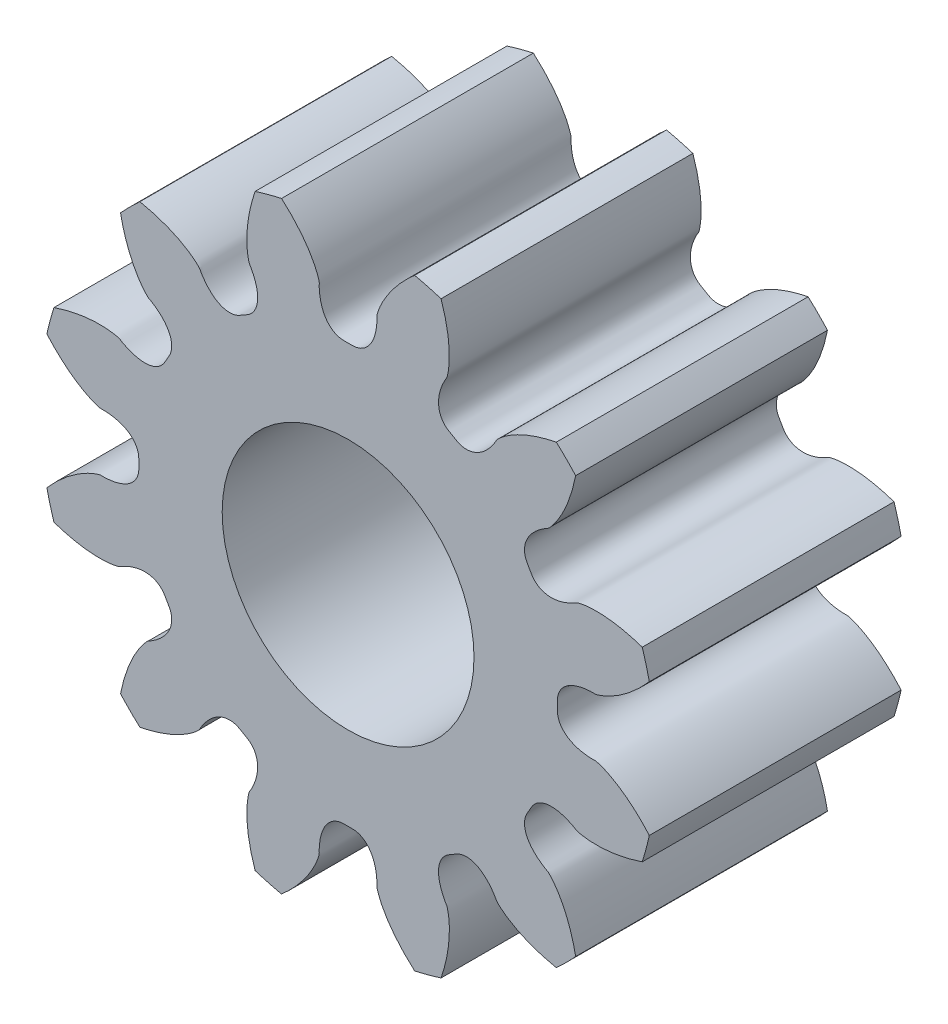
SolidWorks part; units mm, degrees
ref_plane "Front" through (0, 0, 0) normal (0, 0, 1) x (1, 0, 0)
ref_plane "Top" through (0, 0, 0) normal (0, 1, 0) x (1, 0, 0)
ref_plane "Right" through (0, 0, 0) normal (1, 0, 0) x (0, 0, -1)
ref_axis "Axis1" through (0, 0, 50) along (0, 0, -1)
sketch "SketchRevolveSpur01" plane through (0, 0, 0) normal (1, 0, 0) x (0, 0, -1)
  line L0 (0, 0) -> (1, 0) construction
  line L1 (-3, 0) -> (-3, 7.35)
  line L2 (-3, 7.35) -> (3, 7.35)
  line L3 (3, 7.35) -> (3, 0)
  line L4 (3, 0) -> (-3, 0)
  dimension "Side1" = 3
  dimension "OutsideRadius" = 7.35
  dimension "Side2" = 3
revolve "Spur01" add sketch "SketchRevolveSpur01" angle 360 about L0
sketch "SketchToothSpur01" plane through (0, 0, 0) normal (0, 0, 1) x (1, 0, 0)
  arc A0 (7.2196, 1.6352) -> (7.2196, -1.6352) centre (0, 0) cw
  spline S0 degree 3 poles (7.2196, -1.6352) (7.1512, -1.5547) (7.0472, -1.4407) (6.9039, -1.3008) (6.8019, -1.2084) (6.7029, -1.1253) (6.6074, -1.051) (6.5159, -0.9853) (6.4291, -0.9276) (6.3472, -0.8776) (6.2708, -0.8348) (6.2003, -0.7986) (6.136, -0.7687) (6.0784, -0.7445) (6.0276, -0.7251) (5.9684, -0.706) (5.9004, -0.6821) (5.8258, -0.69) (5.7634, -0.6863) (5.7097, -0.6827) (5.6575, -0.6771) (5.6068, -0.6697) (5.5575, -0.6606) (5.5097, -0.6498) (5.4633, -0.6371) (5.4183, -0.6226) (5.3747, -0.6063) (5.3325, -0.5879) (5.2917, -0.5674) (5.2522, -0.5447) (5.2142, -0.5194) (5.1776, -0.4914) (5.1428, -0.4603) (5.1098, -0.4258) (5.0793, -0.3877) (5.0516, -0.3455) (5.0276, -0.2994) (5.0082, -0.2493) (4.9943, -0.1958) (4.988, -0.1455) (4.9854, -0.08) (4.989, 0) (4.9854, 0.08) (4.988, 0.1455) (4.9943, 0.1958) (5.0082, 0.2493) (5.0276, 0.2994) (5.0516, 0.3455) (5.0793, 0.3877) (5.1098, 0.4258) (5.1428, 0.4603) (5.1776, 0.4914) (5.2142, 0.5194) (5.2522, 0.5447) (5.2917, 0.5674) (5.3325, 0.5879) (5.3747, 0.6063) (5.4183, 0.6226) (5.4633, 0.6371) (5.5097, 0.6498) (5.5575, 0.6606) (5.6068, 0.6697) (5.6575, 0.6771) (5.7097, 0.6827) (5.7634, 0.6863) (5.8258, 0.69) (5.9004, 0.6821) (5.9684, 0.706) (6.0276, 0.7251) (6.0784, 0.7445) (6.136, 0.7687) (6.2003, 0.7986) (6.2708, 0.8348) (6.3472, 0.8776) (6.4291, 0.9276) (6.5159, 0.9853) (6.6074, 1.051) (6.7029, 1.1253) (6.8019, 1.2084) (6.9039, 1.3008) (7.0472, 1.4407) (7.1512, 1.5547) (7.2196, 1.6352) knots 0 0 0 0 0.053494 0.07813 0.101357 0.123177 0.143589 0.162594 0.180191 0.19638 0.211161 0.224534 0.2365 0.247058 0.256209 0.263951 0.278695 0.292012 0.301319 0.310395 0.31925 0.327895 0.336345 0.344615 0.352721 0.360686 0.368533 0.376288 0.383984 0.391656 0.399345 0.407095 0.414956 0.422977 0.431208 0.439691 0.448455 0.457508 0.466829 0.476365 0.48311 0.5 0.51689 0.523635 0.533171 0.542492 0.551545 0.560309 0.568792 0.577023 0.585044 0.592905 0.600655 0.608344 0.616016 0.623712 0.631467 0.639314 0.647279 0.655385 0.663655 0.672105 0.68075 0.689605 0.698681 0.707988 0.721305 0.736049 0.743791 0.752942 0.7635 0.775466 0.788839 0.80362 0.819809 0.837406 0.856411 0.876823 0.898643 0.92187 0.946506 1 1 1 1
extrude "ToothExtrudeCutSpur01" cut sketch "SketchToothSpur01" against normal blind 3 and the other way blind 3
pattern_circular "PatternSpur01" count 12 every 30 about axis through (0, 0, 50) along (0, 0, -1) of "ToothExtrudeCutSpur01"
sketch "BoreRevolveSketch" plane through (0, 0, 0) normal (1, 0, 0) x (0, 0, -1)
  line L0 (0, 0) -> (1, 0) construction
  line L1 (-3, 0) -> (3, 0)
  line L2 (3, 0) -> (3, 3)
  line L3 (3, 3) -> (-3, 3)
  line L4 (-3, 3) -> (-3, 0)
  dimension "BoreSide1" = 3
  dimension "TaperSide1" = 3
  dimension "BoreSide2" = 3
  dimension "TaperSide2" = 3
revolve "BoreRevolveCut" cut sketch "BoreRevolveSketch" angle 360 about L0
